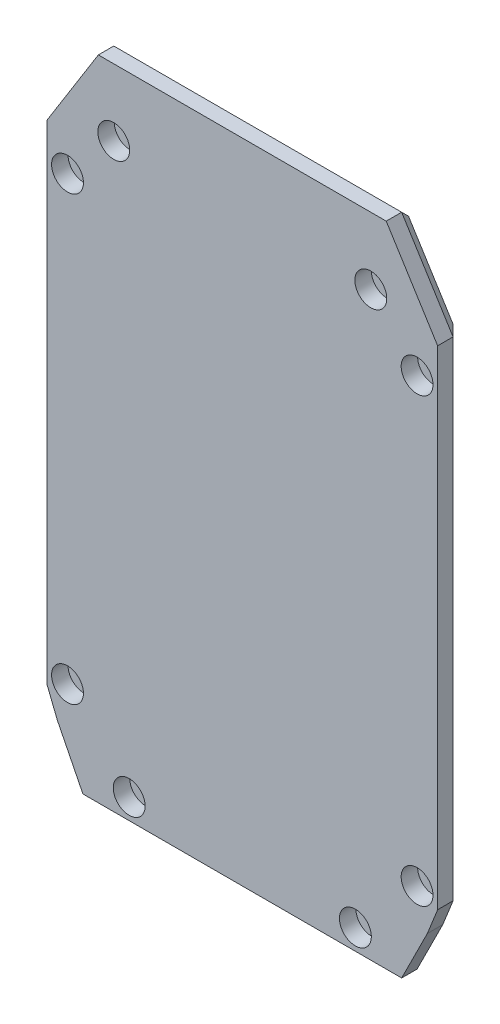
SolidWorks part; units mm, degrees
material "深灰橡胶_暂定1150kg_m3"
ref_plane "前视基准面" through (0, 0, 0) normal (0, 0, 1) x (1, 0, 0)
ref_plane "上视基准面" through (0, 0, 0) normal (0, 1, 0) x (1, 0, 0)
ref_plane "右视基准面" through (0, 0, 0) normal (1, 0, 0) x (0, 0, -1)
other "Configuration Table"
sketch "草图1" plane through (0, 0, 0) normal (0, 0, 1) x (1, 0, 0)
  line L0 (-31, -60) -> (31, -60)
  line L1 (31, -60) -> (36, -50)
  line L2 (36, -50) -> (38, -45)
  line L3 (38, -45) -> (38, 50)
  line L4 (38, 50) -> (28, 66)
  line L5 (28, 66) -> (-28, 66)
  line L6 (-28, 66) -> (-38, 50)
  line L7 (-38, 50) -> (-38, -45)
  line L8 (-38, -45) -> (-36, -50)
  line L9 (-36, -50) -> (-31, -60)
extrude "六毫米深灰橡胶底垫" add sketch "草图1" along normal blind 6
chamfer "橡胶垫全周向心倒角_C3" distance 3 angle 45 10 edges at (-33.5, -55, 0) (0, -60, 0) (33.5, -55, 0) (37, -47.5, 0) (38, 2.5, 0) (33, 58, 0) (0, 66, 0) (-33, 58, 0) (-38, 2.5, 0) (-37, -47.5, 0)
sketch "草图2" plane through (0, 0, 0) normal (0, 0, 1) x (1, 0, 0)
  line L0 (-28.9, -46.1) -> (28.9, -46.1)
  line L1 (28.9, -43.9) -> (-28.9, -43.9)
  line L2 (-28.9, -37.1) -> (28.9, -37.1)
  line L3 (28.9, -34.9) -> (-28.9, -34.9)
  line L4 (-28.9, -28.1) -> (28.9, -28.1)
  line L5 (28.9, -25.9) -> (-28.9, -25.9)
  line L6 (-28.9, -19.1) -> (28.9, -19.1)
  line L7 (28.9, -16.9) -> (-28.9, -16.9)
  line L8 (-28.9, -10.1) -> (28.9, -10.1)
  line L9 (28.9, -7.9) -> (-28.9, -7.9)
  line L10 (-28.9, -1.1) -> (28.9, -1.1)
  line L11 (28.9, 1.1) -> (-28.9, 1.1)
  line L12 (-28.9, 7.9) -> (28.9, 7.9)
  line L13 (28.9, 10.1) -> (-28.9, 10.1)
  line L14 (-28.9, 16.9) -> (28.9, 16.9)
  line L15 (28.9, 19.1) -> (-28.9, 19.1)
  line L16 (-28.9, 25.9) -> (28.9, 25.9)
  line L17 (28.9, 28.1) -> (-28.9, 28.1)
  line L18 (-28.9, 34.9) -> (28.9, 34.9)
  line L19 (28.9, 37.1) -> (-28.9, 37.1)
  line L20 (-28.9, 43.9) -> (28.9, 43.9)
  line L21 (28.9, 46.1) -> (-28.9, 46.1)
  line L22 (-28.9, 52.9) -> (28.9, 52.9)
  line L23 (28.9, 55.1) -> (-28.9, 55.1)
  arc A0 (28.9, -46.1) -> (28.9, -43.9) centre (28.9, -45) ccw
  arc A1 (-28.9, -43.9) -> (-28.9, -46.1) centre (-28.9, -45) ccw
  arc A2 (28.9, -37.1) -> (28.9, -34.9) centre (28.9, -36) ccw
  arc A3 (-28.9, -34.9) -> (-28.9, -37.1) centre (-28.9, -36) ccw
  arc A4 (28.9, -28.1) -> (28.9, -25.9) centre (28.9, -27) ccw
  arc A5 (-28.9, -25.9) -> (-28.9, -28.1) centre (-28.9, -27) ccw
  arc A6 (28.9, -19.1) -> (28.9, -16.9) centre (28.9, -18) ccw
  arc A7 (-28.9, -16.9) -> (-28.9, -19.1) centre (-28.9, -18) ccw
  arc A8 (28.9, -10.1) -> (28.9, -7.9) centre (28.9, -9) ccw
  arc A9 (-28.9, -7.9) -> (-28.9, -10.1) centre (-28.9, -9) ccw
  arc A10 (28.9, -1.1) -> (28.9, 1.1) centre (28.9, 0) ccw
  arc A11 (-28.9, 1.1) -> (-28.9, -1.1) centre (-28.9, 0) ccw
  arc A12 (28.9, 7.9) -> (28.9, 10.1) centre (28.9, 9) ccw
  arc A13 (-28.9, 10.1) -> (-28.9, 7.9) centre (-28.9, 9) ccw
  arc A14 (28.9, 16.9) -> (28.9, 19.1) centre (28.9, 18) ccw
  arc A15 (-28.9, 19.1) -> (-28.9, 16.9) centre (-28.9, 18) ccw
  arc A16 (28.9, 25.9) -> (28.9, 28.1) centre (28.9, 27) ccw
  arc A17 (-28.9, 28.1) -> (-28.9, 25.9) centre (-28.9, 27) ccw
  arc A18 (28.9, 34.9) -> (28.9, 37.1) centre (28.9, 36) ccw
  arc A19 (-28.9, 37.1) -> (-28.9, 34.9) centre (-28.9, 36) ccw
  arc A20 (28.9, 43.9) -> (28.9, 46.1) centre (28.9, 45) ccw
  arc A21 (-28.9, 46.1) -> (-28.9, 43.9) centre (-28.9, 45) ccw
  arc A22 (28.9, 52.9) -> (28.9, 55.1) centre (28.9, 54) ccw
  arc A23 (-28.9, 55.1) -> (-28.9, 52.9) centre (-28.9, 54) ccw
extrude "鞋底横向等距防滑槽_节距9_深1p5" cut sketch "草图2" along normal blind 1.5
sketch "草图3" plane through (0, 0, 0) normal (0, 0, 1) x (1, 0, 0)
  line L0 (-14.1, -46) -> (-13.9, -46)
  line L1 (-12.9, -45) -> (-12.9, 51)
  line L2 (-13.9, 52) -> (-14.1, 52)
  line L3 (-15.1, 51) -> (-15.1, -45)
  line L4 (13.9, -46) -> (14.1, -46)
  line L5 (15.1, -45) -> (15.1, 51)
  line L6 (14.1, 52) -> (13.9, 52)
  line L7 (12.9, 51) -> (12.9, -45)
  arc A0 (-13.9, -46) -> (-12.9, -45) centre (-13.9, -45) ccw
  arc A1 (-12.9, 51) -> (-13.9, 52) centre (-13.9, 51) ccw
  arc A2 (-14.1, 52) -> (-15.1, 51) centre (-14.1, 51) ccw
  arc A3 (-15.1, -45) -> (-14.1, -46) centre (-14.1, -45) ccw
  arc A4 (14.1, -46) -> (15.1, -45) centre (14.1, -45) ccw
  arc A5 (15.1, 51) -> (14.1, 52) centre (14.1, 51) ccw
  arc A6 (13.9, 52) -> (12.9, 51) centre (13.9, 51) ccw
  arc A7 (12.9, -45) -> (13.9, -46) centre (13.9, -45) ccw
extrude "鞋底纵向分区槽_深1p5" cut sketch "草图3" along normal blind 1.5
sketch "草图4" plane through (0, 0, 0) normal (0, 0, 1) x (1, 0, 0)
  circle A0 centre (-22, -56) radius 3.1
  circle A1 centre (-25, 53) radius 3.1
  circle A2 centre (-34, -43) radius 3.1
  circle A3 centre (-34, 43) radius 3.1
  circle A4 centre (22, -56) radius 3.1
  circle A5 centre (25, 53) radius 3.1
  circle A6 centre (34, -43) radius 3.1
  circle A7 centre (34, 43) radius 3.1
extrude "底部螺钉头背面避让_保留2p8底厚" cut sketch "草图4" along normal blind 3.2 from offset 2.8
